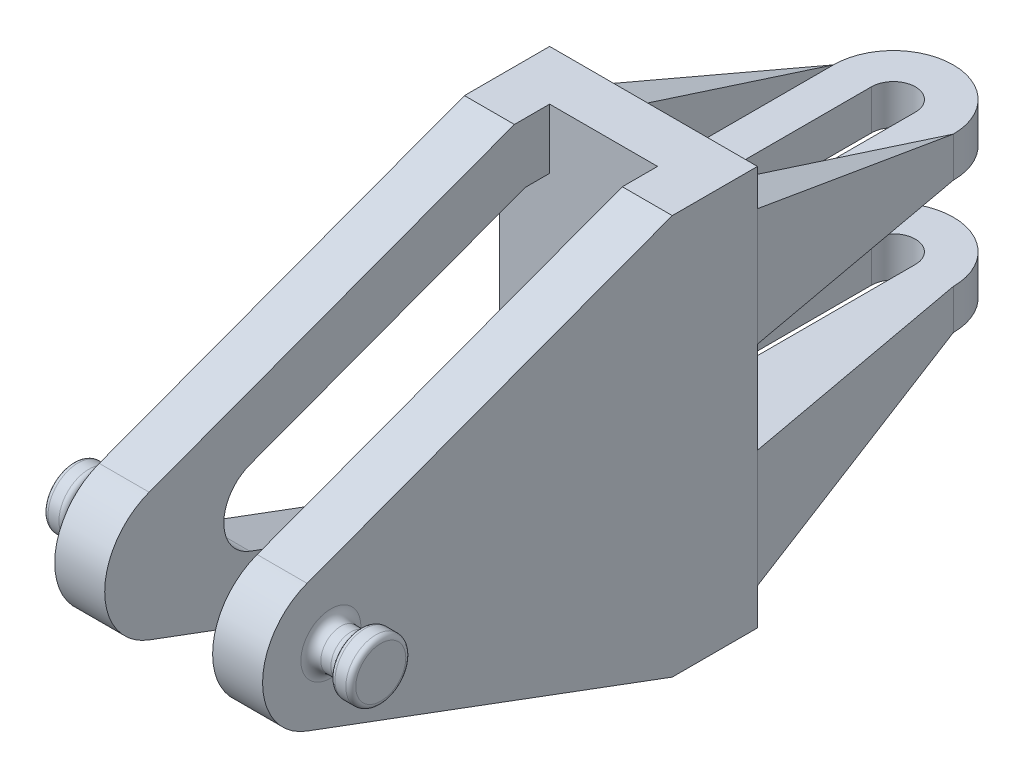
SolidWorks part; units mm, degrees
ref_plane "Front Plane" through (0, 0, 0) normal (0, 0, 1) x (1, 0, 0)
ref_plane "Top Plane" through (0, 0, 0) normal (0, 1, 0) x (1, 0, 0)
ref_plane "Right Plane" through (0, 0, 0) normal (1, 0, 0) x (0, 0, -1)
sketch "Sketch1" plane through (0, 0, 0) normal (0, 1, 0) x (1, 0, 0)
  line L0 (15.8, 0) -> (20.8, 0)
  line L1 (0, 0) -> (5, 0)
  line L2 (0, 0) -> (0, 55)
  line L3 (0, 55) -> (20.8, 55)
  line L4 (20.8, 0) -> (20.8, 55)
  line L6 (5, 0) -> (5, 50)
  line L7 (5, 50) -> (15.8, 50)
  line L8 (15.8, 0) -> (15.8, 50)
  dimension "D1" = 10.8
  dimension "D2" = 50
  dimension "D3" = 55
  dimension "D4" = 5
  dimension "D5" = 5
extrude "Boss-Extrude1" add sketch "Sketch1" along normal blind 40
sketch "Sketch2" plane through (20.8, 0, 0) normal (1, 0, 0) x (0, 0, -1)
  line L0 (46.4743, 40) -> (9.9231, 26.4027)
  line L1 (0, 40) -> (55, 40) construction
  line L2 (46.4743, 0) -> (9.923, 13.5978)
  line L3 (0, 0) -> (55, 0) construction
  line L4 (46.4743, 40) -> (0, 40)
  line L5 (0, 40) -> (0, 0)
  line L6 (0, 0) -> (46.4743, 0)
  arc A0 (9.9231, 26.4027) -> (9.923, 13.5978) centre (12.3049, 20.0003) ccw
extrude "Cut-Extrude1" cut sketch "Sketch2" against normal blind 40
sketch "Sketch4" plane through (0, 0, 0) normal (-1, 0, 0) x (0, 0, 1)
  circle A0 centre (-12.3049, 20.0003) radius 2
  dimension "D1" = 4
extrude "Boss-Extrude2" add sketch "Sketch4" along normal blind 3
sketch "Sketch5" plane through (-3, 0, 0) normal (-1, 0, 0) x (0, 0, 1)
  circle A0 centre (-12.3049, 20.0003) radius 3
  dimension "D1" = 6
extrude "Boss-Extrude3" add sketch "Sketch5" along normal blind 2
sketch "Sketch6" plane through (20.8, 0, 0) normal (1, 0, 0) x (0, 0, -1)
  circle A0 centre (12.3049, 20.0003) radius 2
  dimension "D1" = 4
extrude "Boss-Extrude4" add sketch "Sketch6" along normal blind 3
sketch "Sketch7" plane through (23.8, 0, 0) normal (1, 0, 0) x (0, 0, -1)
  circle A0 centre (12.3049, 20.0003) radius 3
  dimension "D1" = 6
extrude "Boss-Extrude5" add sketch "Sketch7" along normal blind 2
fillet "Fillet1" radius 1 4 edges at (20.8, 20.0003, -10.3049) (23.8, 20.0003, -14.3049) (0, 20.0003, -14.3049) (-3, 20.0003, -10.3049)
fillet "Fillet2" radius 0.5 4 edges at (-3, 20.0003, -9.3049) (-5, 20.0003, -9.3049) (25.8, 20.0003, -15.3049) (23.8, 20.0003, -15.3049)
sketch "Sketch8" plane through (0, 0, 0) normal (-1, 0, 0) x (0, 0, 1)
  line L0 (-46.4743, 0) -> (-9.923, 13.5978) construction
  line L1 (-9.9231, 26.4027) -> (-46.4743, 40) construction
  line L2 (-50, 34) -> (-50, 6)
  line L3 (-55, 40) -> (-55, 0) construction
  line L4 (-19.9987, 23.7492) -> (-47.5541, 34)
  line L5 (-47.5542, 6) -> (-19.9987, 16.2512)
  line L6 (-50, 34) -> (-47.5541, 34)
  line L7 (-47.5542, 6) -> (-50, 6)
  line L8 (-55, 0) -> (-46.4743, 0) construction
  line L9 (-55, 40) -> (-46.4743, 40) construction
  arc A0 (-19.9987, 16.2512) -> (-19.9987, 23.7492) centre (-21.3934, 20.0002) ccw
  dimension "D4" = 4
  dimension "D1" = 5
  dimension "D2" = 6
  dimension "D3" = 6
  dimension "D5" = 6
  dimension "D6" = 6
extrude "Cut-Extrude2" cut sketch "Sketch8" against normal blind 5
sketch "Sketch10" plane through (0, 0, -55) normal (0, 0, -1) x (-1, 0, 0)
  line L1 (-16.4, 24.6) -> (-4.4, 24.6)
  line L2 (-16.4, 24.6) -> (-16.4, 28.6)
  line L3 (-16.4, 28.6) -> (-4.4, 28.6)
  line L4 (-4.4, 24.6) -> (-4.4, 28.6)
  line L7 (-16.4, 11.4) -> (-4.4, 11.4)
  line L8 (-16.4, 11.4) -> (-16.4, 15.4)
  line L9 (-16.4, 15.4) -> (-4.4, 15.4)
  line L10 (-4.4, 11.4) -> (-4.4, 15.4)
  line L11 (-20.8, 40) -> (-20.8, 0) construction
  line L12 (-20.8, 0) -> (0, 0) construction
  dimension "D1" = 9.2
  dimension "D2" = 4
  dimension "D3" = 4
  dimension "D4" = 12
  dimension "D5" = 12
  dimension "D6" = 4.4
  dimension "D7" = 4.4
  dimension "D8" = 11.4
extrude "Boss-Extrude6" add sketch "Sketch10" along normal blind 30
sketch "Sketch11" plane through (0, 11.4, 0) normal (0, -1, 0) x (1, 0, 0)
  line L0 (4.4, -85) -> (4.4, -55) construction
  line L1 (16.4, -85) -> (4.4, -85) construction
  line L2 (4.4, -79) -> (4.4, -85)
  line L3 (4.4, -85) -> (16.4, -85)
  line L4 (16.4, -85) -> (16.4, -79)
  arc A0 (4.4, -79) -> (16.4, -79) centre (10.4, -79) ccw
  line M2 (4.4, -55) -> (4.4, -85)
  line M3 (4.4, -85) -> (16.4, -85)
  line M4 (16.4, -85) -> (16.4, -55)
  dimension "D1" = 12
  dimension "D2" = 6
  dimension "D3" = 6
extrude "Cut-Extrude3" cut sketch "Sketch11" against normal blind 30 contours A0 L3 M4 | A0 M2 M3 region at (5.7402, 11.4, -83.6598) region at (15.0598, 11.4, -83.6598)
sketch "Sketch12" plane through (0, 11.4, 0) normal (0, -1, 0) x (1, 0, 0)
  line L0 (10.4, -79) -> (10.4, -55) construction
  line L1 (16.4, -55) -> (4.4, -55) construction
  line L2 (8.2, -79) -> (8.2, -55)
  line L3 (12.6, -79) -> (12.6, -55)
  line L4 (8.2, -55) -> (12.6, -55)
  arc A0 (8.2, -79) -> (12.6, -79) centre (10.4, -79) ccw
  point P5 (10.4, -67)
  dimension "D1" = 2.2
extrude "Cut-Extrude4" cut sketch "Sketch12" against normal blind 30
sketch "Sketch13" plane through (16.4, 0, 0) normal (1, 0, 0) x (0, 0, -1)
  line L1 (55, 28.6) -> (55, 36.3357)
  line L2 (55, 36.3357) -> (79, 28.6)
  line L3 (55, 28.6) -> (55, 24.6)
  line L4 (55, 24.6) -> (79, 24.6)
  line L5 (79, 24.6) -> (79, 28.6)
  line L6 (55, 3.6643) -> (79, 11.4)
  line L8 (55, 11.4) -> (55, 3.6643)
  line L9 (55, 11.4) -> (55, 15.4)
  line L10 (79, 15.4) -> (79, 11.4)
  line L11 (55, 15.4) -> (79, 15.4)
extrude "Boss-Extrude7" add sketch "Sketch13" along normal blind 4.4
sketch "Sketch14" plane through (4.4, 0, 0) normal (-1, 0, 0) x (0, 0, 1)
  line L0 (-55, 3.6643) -> (-79, 11.4) construction
  line L1 (-79, 11.4) -> (-79, 15.4) construction
  line L2 (-79, 15.4) -> (-55, 15.4) construction
  line L3 (-79, 24.6) -> (-79, 28.6) construction
  line L4 (-55, 24.6) -> (-79, 24.6) construction
  line L5 (-79, 28.6) -> (-55, 36.3357) construction
  line L6 (-55, 3.6643) -> (-79, 11.4)
  line L7 (-79, 11.4) -> (-79, 15.4)
  line L8 (-79, 15.4) -> (-55, 15.4)
  line L9 (-79, 24.6) -> (-79, 28.6)
  line L10 (-55, 24.6) -> (-79, 24.6)
  line L11 (-79, 28.6) -> (-55, 36.3357)
  line L12 (-55, 24.6) -> (-55, 36.3357)
  line L13 (-55, 3.6643) -> (-55, 15.4)
extrude "Boss-Extrude8" add sketch "Sketch14" along normal blind 4.4
sketch "Sketch15" plane through (0, 0, 0) normal (0, -1, 0) x (1, 0, 0)
  line L0 (16.4, -79) -> (20.8, -55)
  line L1 (4.4, -79) -> (0, -55)
  line L2 (0, -79) -> (4.4, -79) construction
  line L3 (0, -55) -> (0, -79)
  line L4 (0, -79) -> (4.4, -79)
  line L5 (16.4, -79) -> (20.8, -79)
  line L6 (20.8, -79) -> (20.8, -55)
  arc A0 (4.4, -79) -> (16.4, -79) centre (10.4, -79) ccw construction
extrude "Cut-Extrude5" cut sketch "Sketch15" against normal through all
